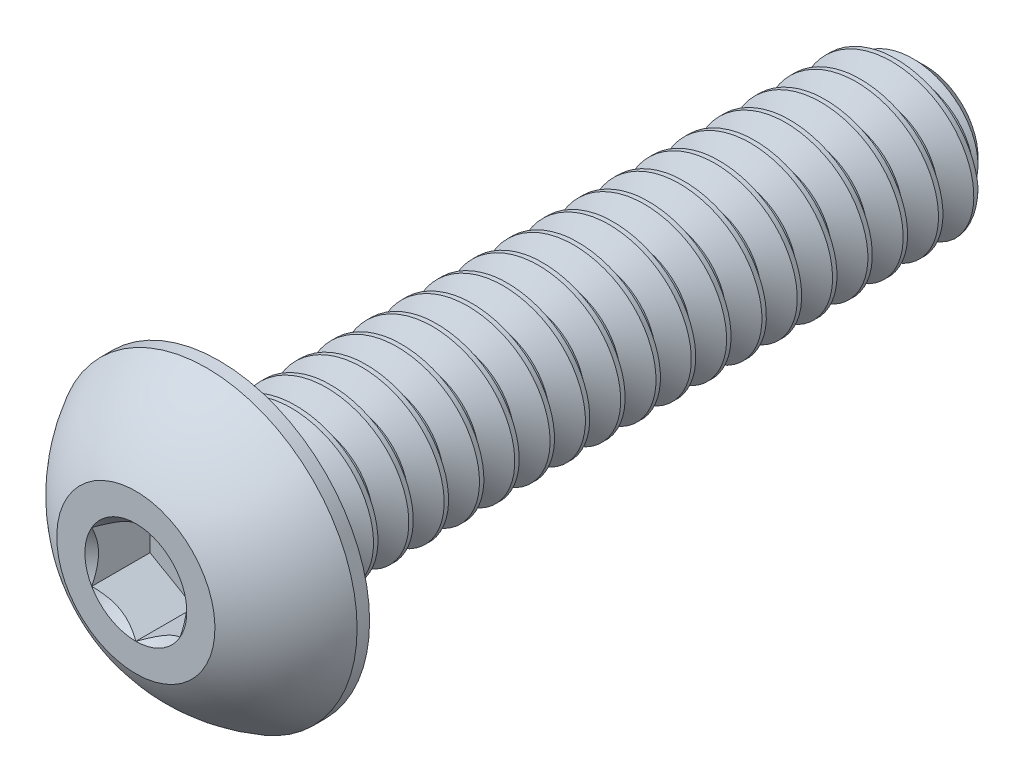
SolidWorks part; units mm, degrees
material "AISI 304"
ref_plane "Front" through (0, 0, 0) normal (0, 0, 1) x (1, 0, 0)
ref_plane "Top" through (0, 0, 0) normal (0, 1, 0) x (1, 0, 0)
ref_plane "Right" through (0, 0, 0) normal (1, 0, 0) x (0, 0, -1)
sketch "Sketch1" plane through (0, 0, 0) normal (1, 0, 0) x (0, 0, -1)
  line L2 (1.4986, 1.4224) -> (14.1986, 1.4224)
  line L3 (14.1986, 1.4224) -> (14.1986, 0)
  line L4 (14.1986, 0) -> (1.4986, 0)
  line L6 (1.2738, 2.7051) -> (1.4986, 2.7051) construction
  line L7 (14.1986, 1.4224) -> (14.1986, -1.4224) construction
  line L8 (0, 0) -> (1.4986, 0) construction
  line L9 (1.4986, 2.7051) -> (1.4986, -2.7051) construction
  line L11 (1.4986, 1.4224) -> (1.4986, 0)
  line L13 (0, 0.7937) -> (0, -0.7937) construction
  line L14 (0, 0.7937) -> (0, 1.4224) construction
  arc A3 (0, 1.4224) -> (1.2738, 2.7051) centre (2.7151, 0) cw construction
  dimension "D1" = 0.2248
  dimension "Head Ht" = 1.4986
  dimension "Head Dia" = 5.4102
  dimension "Dia" = 2.8448
  dimension "Lg" = 12.7
  dimension "Hex" = 1.5875
revolve "Revolve1" add sketch "Sketch1" angle 360 mid plane about L4
sketch "Sketch3" plane through (0, 0, -14.1986) normal (0, 0, -1) x (-1, 0, 0)
  circle A0 centre (0, 0) radius 1.4224
curve "Helix/Spiral1" pitch 0.635 height 13.335 radius 1.4224 centre (0, 0, -14.1986) axis (0, 0, 1) start towards (0, 1, 0)
sketch "Sketch2" plane through (0, 0, 0) normal (1, 0, 0) x (0, 0, -1)
  line L0 (14.1986, 1.4224) -> (14.7542, 1.4224)
  line L1 (14.7542, 1.4224) -> (14.5161, 1.01)
  line L2 (14.5161, 1.01) -> (14.4367, 1.01)
  line L3 (14.4367, 1.01) -> (14.1986, 1.4224)
  line L4 (14.3177, 1.2162) -> (14.6352, 1.2162) construction
  dimension "D1" = 60
  dimension "D2" = 0.0794
  dimension "D3" = 0.3175
chamfer "Chamfer1" distance 0.4763 angle 45 1 edges at (0, 1.4224, -14.1986)
sweep "Cut-Sweep1" cut profiles "Sketch2" path "Helix/Spiral1" align with end faces yes
sketch "Sketch7" plane through (0, 0, 0) normal (1, 0, 0) x (0, 0, -1)
  line L6 (1.2738, 2.7051) -> (1.4986, 2.7051) construction
  line L8 (0, 0) -> (1.4986, 0) construction
  line L11 (1.4986, 2.7051) -> (1.4986, -2.7051) construction
  line L12 (1.2738, 2.7051) -> (1.4986, 2.7051)
  line L13 (0, 0) -> (1.4986, 0)
  line L14 (0, 0.7937) -> (0, -0.7937) construction
  line L15 (1.4986, 2.7051) -> (1.4986, 0)
  line L16 (0, 1.4224) -> (0, 0)
  arc A2 (1.2738, 2.7051) -> (0, 1.4224) centre (2.7151, 0) ccw construction
  arc A3 (1.2738, 2.7051) -> (0, 1.4224) centre (2.7151, 0) ccw
revolve "Revolve2" add sketch "Sketch7" angle 360 mid plane about L13
sketch "Sketch5" plane through (0, 0, 0) normal (0, 0, 1) x (1, 0, 0)
  line L1 (0.7937, -0.4583) -> (0.7937, 0.4583)
  line L2 (0.7937, 0.4583) -> (0, 0.9165)
  line L3 (0, 0.9165) -> (-0.7937, 0.4583)
  line L4 (-0.7937, 0.4583) -> (-0.7937, -0.4583)
  line L5 (-0.7937, -0.4583) -> (0, -0.9165)
  line L6 (0, -0.9165) -> (0.7937, -0.4583)
  circle A0 centre (0, 0) radius 0.7937 construction
extrude "Cut-Extrude2" cut sketch "Sketch5" against normal blind 1.049
sketch "Sketch6" plane through (0, 0, 0) normal (0, 0, 1) x (1, 0, 0)
  circle A0 centre (0, 0) radius 0.9165
extrude "Cut-Extrude3" cut sketch "Sketch6" against normal blind 1.049 draft 45
sketch "Sketch9" [suppressed] plane through (0, 0, -1.4986) normal (0, 0, 1) x (1, 0, 0)
  circle A2 centre (0, 0) radius 1.4224
extrude "Boss-Extrude2" [suppressed] add sketch "Sketch9" against normal offset from surface (12.7 mm away) 31.75 up to face at (0, 0.9462, -14.1986)
sketch "Sketch10" plane through (0, 0, 0) normal (1, 0, 0) x (0, 0, -1)
  line L0 (14.1986, 1.4224) -> (14.1986, -1.4224) construction
  point P0 (13.2461, -1.4224)
  dimension "D1" = 0.9525
equation "\"D3@Helix/Spiral1\" = \"Lg@Sketch1\" + \"D4@Helix/Spiral1\""
equation "\"D2@Sketch2\" = \"D4@Helix/Spiral1\" * .125"
equation "\"D3@Sketch2\" = \"D4@Helix/Spiral1\" * .5"
equation "\"D1@Chamfer1\" = \"D4@Helix/Spiral1\" * .75"
equation "\"D1@Cut-Extrude2\" = \"Head Ht@Sketch1\" * .7"
equation "\"D1@Sketch1\" = \"Head Ht@Sketch1\" * .15"
equation "\"D1@Sketch10\" = \"D4@Helix/Spiral1\" * 1.5"
equation "\"D1@Cut-Extrude3\" = \"D1@Cut-Extrude2\""
